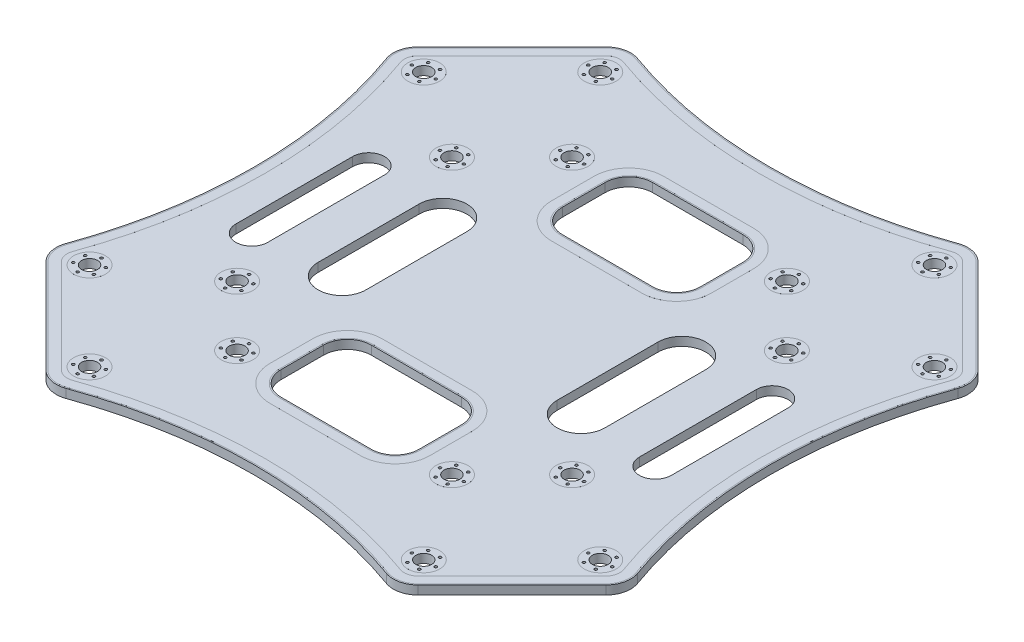
SolidWorks part; units mm, degrees
material "PLA"
ref_plane "Front Plane" through (0, 0, 0) normal (0, 0, 1) x (1, 0, 0)
ref_plane "Top Plane" through (0, 0, 0) normal (0, 1, 0) x (1, 0, 0)
ref_plane "Right Plane" through (0, 0, 0) normal (1, 0, 0) x (0, 0, -1)
sketch "Sketch1" plane through (0, 0, 0) normal (0, 1, 0) x (1, 0, 0)
  line L0 (-48.55, 0) -> (48.55, 0) construction
  line L1 (0, 48.55) -> (0, -48.55) construction
  line L2 (-30.1605, 53.8) -> (30.1605, 53.8) construction
  line L3 (0, 48.55) -> (0, 53.8) construction
  line L4 (-53.8, 30.1605) -> (-53.8, -30.1605) construction
  line L5 (-30.1605, -53.8) -> (30.1605, -53.8) construction
  line L6 (53.8, -30.1605) -> (53.8, 30.1605) construction
  line L7 (35.0464, 52.7056) -> (52.7056, 35.0464)
  line L8 (-52.7056, 35.0464) -> (-35.0464, 52.7056)
  line L9 (-52.7056, -35.0464) -> (-35.0464, -52.7056)
  line L10 (35.0464, -52.7056) -> (52.7056, -35.0464)
  line L11 (-43.876, -43.876) -> (43.876, 43.876) construction
  line L12 (-43.876, 43.876) -> (43.876, -43.876) construction
  line L13 (-31.7403, 54.075) -> (-31.7403, -54.075) construction
  line L14 (-31.7403, -54.075) -> (31.7403, -54.075) construction
  arc A0 (-30.1605, 53.8) -> (30.1605, 53.8) centre (0, 137.8088) ccw
  arc A1 (53.8, 30.1605) -> (53.8, -30.1605) centre (137.8088, 0) ccw
  arc A2 (30.1605, -53.8) -> (-30.1605, -53.8) centre (0, -137.8088) ccw
  arc A3 (-53.8, -30.1605) -> (-53.8, 30.1605) centre (-137.8088, 0) ccw
  arc A4 (-53.8, -30.1605) -> (-52.7056, -35.0464) centre (-49.3995, -31.7403) ccw
  arc A5 (-35.0464, -52.7056) -> (-30.1605, -53.8) centre (-31.7403, -49.3995) ccw
  arc A6 (30.1605, -53.8) -> (35.0464, -52.7056) centre (31.7403, -49.3995) ccw
  arc A7 (52.7056, -35.0464) -> (53.8, -30.1605) centre (49.3995, -31.7403) ccw
  arc A8 (53.8, 30.1605) -> (52.7056, 35.0464) centre (49.3995, 31.7403) ccw
  arc A9 (35.0464, 52.7056) -> (30.1605, 53.8) centre (31.7403, 49.3995) ccw
  arc A10 (-30.1605, 53.8) -> (-35.0464, 52.7056) centre (-31.7403, 49.3995) ccw
  arc A11 (-52.7056, 35.0464) -> (-53.8, 30.1605) centre (-49.3995, 31.7403) ccw
  point P2 (0, 0)
  point P6 (0, 0)
  point P34 (0, 0)
  dimension "D2" = 108.15
  dimension "D4" = 124.1
  dimension "D1" = 97.1
  dimension "D3" = 5.25
  dimension "D5" = 45
extrude "Boss-Extrude1" add sketch "Sketch1" along normal blind 0.825 and the other way blind 0.825
sketch "Sketch2" plane through (0, 0.825, 0) normal (0, 1, 0) x (1, 0, 0)
  line L0 (0, 18) -> (0, -18) construction
  line L1 (0, 35) -> (0, 18) construction
  line L2 (0, -18) -> (0, -35) construction
  line L3 (-13, 26.5) -> (13, 26.5) construction
  line L4 (13, 30.5) -> (13, 22.5)
  line L5 (-13, 30.5) -> (-13, 22.5)
  line L6 (-8.5, 35) -> (8.5, 35)
  line L7 (-8.5, 18) -> (8.5, 18)
  line L8 (-13, -26.5) -> (13, -26.5) construction
  line L9 (-13, -22.5) -> (-13, -30.5)
  line L10 (13, -22.5) -> (13, -30.5)
  line L11 (-8.5, -18) -> (8.5, -18)
  line L12 (-8.5, -35) -> (8.5, -35)
  line L13 (-18, 0) -> (18, 0) construction
  line L14 (-18, 0) -> (-27, 0) construction
  line L15 (18, 0) -> (27, 0) construction
  line L16 (-22.5, 9.5) -> (-22.5, -9.5) construction
  line L17 (22.5, 9.5) -> (22.5, -9.5) construction
  line L18 (-27, -9.5) -> (-27, 9.5)
  line L19 (-18, -9.5) -> (-18, 9.5)
  line L20 (18, -9.5) -> (18, 9.5)
  line L21 (27, -9.5) -> (27, 9.5)
  line L22 (-35, 0) -> (-27, 0) construction
  line L23 (-41, 0) -> (-35, 0) construction
  line L24 (27, 0) -> (35, 0) construction
  line L25 (35, 0) -> (41, 0) construction
  line L26 (-35, 11) -> (-35, -11)
  line L27 (-41, 11) -> (-41, -11)
  line L28 (-38, 11) -> (-38, -11) construction
  line L29 (35, 11) -> (35, -11)
  line L30 (41, 11) -> (41, -11)
  line L31 (38, 11) -> (38, -11) construction
  arc A0 (-8.5, 35) -> (-13, 30.5) centre (-8.5, 30.5) ccw
  arc A1 (13, 30.5) -> (8.5, 35) centre (8.5, 30.5) ccw
  arc A2 (-13, 22.5) -> (-8.5, 18) centre (-8.5, 22.5) ccw
  arc A3 (8.5, 18) -> (13, 22.5) centre (8.5, 22.5) ccw
  arc A4 (-8.5, -18) -> (-13, -22.5) centre (-8.5, -22.5) ccw
  arc A5 (13, -22.5) -> (8.5, -18) centre (8.5, -22.5) ccw
  arc A6 (8.5, -35) -> (13, -30.5) centre (8.5, -30.5) ccw
  arc A7 (-13, -30.5) -> (-8.5, -35) centre (-8.5, -30.5) ccw
  arc A8 (27, 9.5) -> (18, 9.5) centre (22.5, 9.5) ccw
  arc A9 (18, -9.5) -> (27, -9.5) centre (22.5, -9.5) ccw
  arc A10 (-27, -9.5) -> (-18, -9.5) centre (-22.5, -9.5) ccw
  arc A11 (-18, 9.5) -> (-27, 9.5) centre (-22.5, 9.5) ccw
  arc A12 (-35, 11) -> (-41, 11) centre (-38, 11) ccw
  arc A13 (-41, -11) -> (-35, -11) centre (-38, -11) ccw
  arc A14 (41, 11) -> (35, 11) centre (38, 11) ccw
  arc A15 (35, -11) -> (41, -11) centre (38, -11) ccw
  point P5 (0, 26.5)
  point P22 (0, -26.5)
  point P34 (-22.5, 0)
  point P36 (0, 0)
  point P45 (22.5, 0)
  point P64 (-38, 0)
  point P69 (38, 0)
  dimension "D6" = 26
  dimension "D8" = 36
  dimension "D13" = 8
  dimension "D18" = 22
  dimension "D1" = 36
  dimension "D2" = 17
  dimension "D3" = 17
  dimension "D4" = 26
  dimension "D5" = 8
  dimension "D7" = 8
  dimension "D9" = 9
  dimension "D10" = 9
  dimension "D11" = 19
  dimension "D12" = 19
  dimension "D14" = 8
  dimension "D15" = 6
  dimension "D16" = 6
  dimension "D17" = 22
extrude "Cut-Extrude1" cut sketch "Sketch2" against normal up to surface (1.65 mm away) up to face at (0, -0.825, 0)
sketch "Sketch3" plane through (0, 0.825, 0) normal (0, 1, 0) x (1, 0, 0)
  line L0 (-48.0833, -31.4663) -> (-31.4663, -48.0833) construction
  line L1 (-52.7056, -35.0464) -> (-35.0464, -52.7056) construction
  line L2 (-39.7748, -39.7748) -> (-43.876, -43.876) construction
  line L3 (43.876, -43.876) -> (39.7748, -39.7748) construction
  line L4 (31.4663, -48.0833) -> (48.0833, -31.4663) construction
  line L5 (43.876, 43.876) -> (39.7748, 39.7748) construction
  line L6 (31.4663, 48.0833) -> (48.0833, 31.4663) construction
  line L7 (-43.876, 43.876) -> (-39.7748, 39.7748) construction
  line L8 (-31.4663, 48.0833) -> (-48.0833, 31.4663) construction
  line L9 (-35.0464, 52.7056) -> (-52.7056, 35.0464) construction
  line L10 (52.7056, 35.0464) -> (35.0464, 52.7056) construction
  line L11 (35.0464, -52.7056) -> (52.7056, -35.0464) construction
  line L12 (-31.5403, -20.2266) -> (-20.2266, -31.5403) construction
  line L13 (31.5403, -20.2266) -> (20.2266, -31.5403) construction
  line L14 (-31.5403, 20.2266) -> (-20.2266, 31.5403) construction
  line L15 (20.2266, 31.5403) -> (31.5403, 20.2266) construction
  line L16 (-25.8834, -25.8834) -> (-39.7748, -39.7748) construction
  line L17 (-39.7748, 39.7748) -> (-25.8834, 25.8834) construction
  line L18 (39.7748, 39.7748) -> (25.8834, 25.8834) construction
  line L19 (25.8834, -25.8834) -> (39.7748, -39.7748) construction
  line L20 (-20.2266, -31.5403) -> (-31.4663, -48.0833) construction
  line L21 (-31.5403, -20.2266) -> (-48.0833, -31.4663) construction
  circle A0 centre (-48.0833, -31.4663) radius 1.5
  circle A1 centre (-31.4663, -48.0833) radius 1.5
  circle A2 centre (31.4663, -48.0833) radius 1.5
  circle A3 centre (48.0833, -31.4663) radius 1.5
  circle A4 centre (48.0833, 31.4663) radius 1.5
  circle A5 centre (31.4663, 48.0833) radius 1.5
  circle A6 centre (-31.4663, 48.0833) radius 1.5
  circle A7 centre (-48.0833, 31.4663) radius 1.5
  circle A8 centre (-31.5403, -20.2266) radius 1.5
  circle A9 centre (-20.2266, -31.5403) radius 1.5
  circle A10 centre (-31.5403, 20.2266) radius 1.5
  circle A11 centre (-20.2266, 31.5403) radius 1.5
  circle A12 centre (20.2266, 31.5403) radius 1.5
  circle A13 centre (31.5403, 20.2266) radius 1.5
  circle A14 centre (31.5403, -20.2266) radius 1.5
  circle A15 centre (20.2266, -31.5403) radius 1.5
  dimension "D3" = 3
  dimension "D4" = 20
  dimension "D1" = 23.5
  dimension "D2" = 5.8
  dimension "D5" = 16
extrude "Cut-Extrude2" cut sketch "Sketch3" against normal up to surface (1.65 mm away) up to face at (38, -0.825, 0)
sketch "Sketch4" plane through (0, 0.825, 0) normal (0, 1, 0) x (1, 0, 0)
  line L0 (13.25, -30.5) -> (13.25, -22.5)
  line L1 (-13.25, -30.5) -> (-13.25, -22.5)
  line L2 (-8.5, -17.75) -> (8.5, -17.75)
  line L3 (-8.5, -35.25) -> (8.5, -35.25)
  line L4 (13, -30.5) -> (13, -22.5) construction
  line L5 (15.05, -30.5) -> (15.05, -22.5)
  line L6 (-8.5, -15.95) -> (8.5, -15.95)
  line L7 (-15.05, -30.5) -> (-15.05, -22.5)
  line L8 (-8.5, -37.05) -> (8.5, -37.05)
  line L9 (-8.5, 17.75) -> (8.5, 17.75)
  line L10 (-13.25, 22.5) -> (-13.25, 30.5)
  line L11 (-8.5, 35.25) -> (8.5, 35.25)
  line L12 (13.25, 30.5) -> (13.25, 22.5)
  line L13 (13, 22.5) -> (13, 30.5) construction
  line L14 (15.05, 30.5) -> (15.05, 22.5)
  line L15 (-8.5, 15.95) -> (8.5, 15.95)
  line L16 (-15.05, 22.5) -> (-15.05, 30.5)
  line L17 (-8.5, 37.05) -> (8.5, 37.05)
  line L18 (34.8696, -52.5288) -> (52.5288, -34.8696)
  line L19 (35.0464, -52.7056) -> (52.7056, -35.0464) construction
  line L20 (34.8696, 52.5288) -> (52.5288, 34.8696)
  line L21 (52.7056, 35.0464) -> (35.0464, 52.7056) construction
  line L22 (-52.5288, 34.8696) -> (-34.8696, 52.5288)
  line L23 (-35.0464, 52.7056) -> (-52.7056, 35.0464) construction
  line L24 (-52.5288, -34.8696) -> (-34.8696, -52.5288)
  line L25 (-52.7056, -35.0464) -> (-35.0464, -52.7056) construction
  line L26 (-51.256, 33.5968) -> (-33.5968, 51.256)
  line L27 (33.5968, 51.256) -> (51.256, 33.5968)
  line L28 (33.5968, -51.256) -> (51.256, -33.5968)
  line L29 (-51.256, -33.5968) -> (-33.5968, -51.256)
  line L30 (-31.4663, -45.8333) -> (-31.4663, -46.5833) construction
  line L31 (-29.5177, -46.9583) -> (-31.4663, -45.8333) construction
  line L32 (-31.4663, -45.8333) -> (-33.4148, -46.9583) construction
  line L33 (-33.4148, -46.9583) -> (-33.4148, -49.2083) construction
  line L34 (-33.4148, -49.2083) -> (-31.4663, -50.3333) construction
  line L35 (-31.4663, -50.3333) -> (-29.5177, -49.2083) construction
  line L36 (-29.5177, -49.2083) -> (-29.5177, -46.9583) construction
  line L37 (-31.4663, -45.8333) -> (-31.4663, -45.0833) construction
  line L39 (-48.0833, -29.2163) -> (-50.0318, -30.3413) construction
  line L40 (-50.0318, -30.3413) -> (-50.0318, -32.5913) construction
  line L41 (-50.0318, -32.5913) -> (-48.0833, -33.7163) construction
  line L42 (-48.0833, -33.7163) -> (-46.1347, -32.5913) construction
  line L43 (-46.1347, -32.5913) -> (-46.1347, -30.3413) construction
  line L44 (-46.1347, -30.3413) -> (-48.0833, -29.2163) construction
  line L45 (-31.5403, -17.9766) -> (-33.4888, -19.1016) construction
  line L46 (-33.4888, -19.1016) -> (-33.4888, -21.3516) construction
  line L47 (-33.4888, -21.3516) -> (-31.5403, -22.4766) construction
  line L48 (-31.5403, -22.4766) -> (-29.5917, -21.3516) construction
  line L49 (-29.5917, -21.3516) -> (-29.5917, -19.1016) construction
  line L50 (-29.5917, -19.1016) -> (-31.5403, -17.9766) construction
  line L51 (-20.2266, -29.2903) -> (-22.1751, -30.4153) construction
  line L52 (-22.1751, -30.4153) -> (-22.1751, -32.6653) construction
  line L53 (-22.1751, -32.6653) -> (-20.2266, -33.7903) construction
  line L54 (-20.2266, -33.7903) -> (-18.278, -32.6653) construction
  line L55 (-18.278, -32.6653) -> (-18.278, -30.4153) construction
  line L56 (-18.278, -30.4153) -> (-20.2266, -29.2903) construction
  line L57 (20.2266, 33.7903) -> (18.278, 32.6653) construction
  line L58 (18.278, 32.6653) -> (18.278, 30.4153) construction
  line L59 (18.278, 30.4153) -> (20.2266, 29.2903) construction
  line L60 (20.2266, 29.2903) -> (22.1751, 30.4153) construction
  line L61 (22.1751, 30.4153) -> (22.1751, 32.6653) construction
  line L62 (22.1751, 32.6653) -> (20.2266, 33.7903) construction
  line L63 (31.5403, 22.4766) -> (29.5917, 21.3516) construction
  line L64 (29.5917, 21.3516) -> (29.5917, 19.1016) construction
  line L65 (29.5917, 19.1016) -> (31.5403, 17.9766) construction
  line L66 (31.5403, 17.9766) -> (33.4888, 19.1016) construction
  line L67 (33.4888, 19.1016) -> (33.4888, 21.3516) construction
  line L68 (33.4888, 21.3516) -> (31.5403, 22.4766) construction
  line L69 (48.0833, 33.7163) -> (46.1347, 32.5913) construction
  line L70 (46.1347, 32.5913) -> (46.1347, 30.3413) construction
  line L71 (46.1347, 30.3413) -> (48.0833, 29.2163) construction
  line L72 (48.0833, 29.2163) -> (50.0318, 30.3413) construction
  line L73 (50.0318, 30.3413) -> (50.0318, 32.5913) construction
  line L74 (50.0318, 32.5913) -> (48.0833, 33.7163) construction
  line L75 (31.4663, 50.3333) -> (29.5177, 49.2083) construction
  line L76 (29.5177, 49.2083) -> (29.5177, 46.9583) construction
  line L77 (29.5177, 46.9583) -> (31.4663, 45.8333) construction
  line L78 (31.4663, 45.8333) -> (33.4148, 46.9583) construction
  line L79 (33.4148, 46.9583) -> (33.4148, 49.2083) construction
  line L80 (33.4148, 49.2083) -> (31.4663, 50.3333) construction
  line L81 (-50.3333, 31.4663) -> (-49.2083, 29.5177) construction
  line L82 (-49.2083, 29.5177) -> (-46.9583, 29.5177) construction
  line L83 (-46.9583, 29.5177) -> (-45.8333, 31.4663) construction
  line L84 (-45.8333, 31.4663) -> (-46.9583, 33.4148) construction
  line L85 (-46.9583, 33.4148) -> (-49.2083, 33.4148) construction
  line L86 (-49.2083, 33.4148) -> (-50.3333, 31.4663) construction
  line L87 (-33.7903, 20.2266) -> (-32.6653, 18.278) construction
  line L88 (-32.6653, 18.278) -> (-30.4153, 18.278) construction
  line L89 (-30.4153, 18.278) -> (-29.2903, 20.2266) construction
  line L90 (-29.2903, 20.2266) -> (-30.4153, 22.1751) construction
  line L91 (-30.4153, 22.1751) -> (-32.6653, 22.1751) construction
  line L92 (-32.6653, 22.1751) -> (-33.7903, 20.2266) construction
  line L93 (-22.4766, 31.5403) -> (-21.3516, 29.5917) construction
  line L94 (-21.3516, 29.5917) -> (-19.1016, 29.5917) construction
  line L95 (-19.1016, 29.5917) -> (-17.9766, 31.5403) construction
  line L96 (-17.9766, 31.5403) -> (-19.1016, 33.4888) construction
  line L97 (-19.1016, 33.4888) -> (-21.3516, 33.4888) construction
  line L98 (-21.3516, 33.4888) -> (-22.4766, 31.5403) construction
  line L99 (-29.2163, 48.0833) -> (-30.3413, 50.0318) construction
  line L100 (-30.3413, 50.0318) -> (-32.5913, 50.0318) construction
  line L101 (-32.5913, 50.0318) -> (-33.7163, 48.0833) construction
  line L102 (-33.7163, 48.0833) -> (-32.5913, 46.1347) construction
  line L103 (-32.5913, 46.1347) -> (-30.3413, 46.1347) construction
  line L104 (-30.3413, 46.1347) -> (-29.2163, 48.0833) construction
  line L105 (22.4766, -31.5403) -> (21.3516, -29.5917) construction
  line L106 (21.3516, -29.5917) -> (19.1016, -29.5917) construction
  line L107 (19.1016, -29.5917) -> (17.9766, -31.5403) construction
  line L108 (17.9766, -31.5403) -> (19.1016, -33.4888) construction
  line L109 (19.1016, -33.4888) -> (21.3516, -33.4888) construction
  line L110 (21.3516, -33.4888) -> (22.4766, -31.5403) construction
  line L111 (33.7903, -20.2266) -> (32.6653, -18.278) construction
  line L112 (32.6653, -18.278) -> (30.4153, -18.278) construction
  line L113 (30.4153, -18.278) -> (29.2903, -20.2266) construction
  line L114 (29.2903, -20.2266) -> (30.4153, -22.1751) construction
  line L115 (30.4153, -22.1751) -> (32.6653, -22.1751) construction
  line L116 (32.6653, -22.1751) -> (33.7903, -20.2266) construction
  line L117 (33.7163, -48.0833) -> (32.5913, -46.1347) construction
  line L118 (32.5913, -46.1347) -> (30.3413, -46.1347) construction
  line L119 (30.3413, -46.1347) -> (29.2163, -48.0833) construction
  line L120 (29.2163, -48.0833) -> (30.3413, -50.0318) construction
  line L121 (30.3413, -50.0318) -> (32.5913, -50.0318) construction
  line L122 (32.5913, -50.0318) -> (33.7163, -48.0833) construction
  line L123 (50.3333, -31.4663) -> (49.2083, -29.5177) construction
  line L124 (49.2083, -29.5177) -> (46.9583, -29.5177) construction
  line L125 (46.9583, -29.5177) -> (45.8333, -31.4663) construction
  line L126 (45.8333, -31.4663) -> (46.9583, -33.4148) construction
  line L127 (46.9583, -33.4148) -> (49.2083, -33.4148) construction
  line L128 (49.2083, -33.4148) -> (50.3333, -31.4663) construction
  arc A0 (-8.5, -17.75) -> (-13.25, -22.5) centre (-8.5, -22.5) ccw
  arc A1 (13.25, -22.5) -> (8.5, -17.75) centre (8.5, -22.5) ccw
  arc A2 (-13.25, -30.5) -> (-8.5, -35.25) centre (-8.5, -30.5) ccw
  arc A3 (8.5, -35.25) -> (13.25, -30.5) centre (8.5, -30.5) ccw
  arc A4 (8.5, -35) -> (13, -30.5) centre (8.5, -30.5) ccw construction
  arc A5 (13, -22.5) -> (8.5, -18) centre (8.5, -22.5) ccw construction
  arc A6 (-8.5, -18) -> (-13, -22.5) centre (-8.5, -22.5) ccw construction
  arc A7 (-13, -30.5) -> (-8.5, -35) centre (-8.5, -30.5) ccw construction
  arc A8 (15.05, -22.5) -> (8.5, -15.95) centre (8.5, -22.5) ccw
  arc A9 (-8.5, -15.95) -> (-15.05, -22.5) centre (-8.5, -22.5) ccw
  arc A10 (-15.05, -30.5) -> (-8.5, -37.05) centre (-8.5, -30.5) ccw
  arc A11 (8.5, -37.05) -> (15.05, -30.5) centre (8.5, -30.5) ccw
  arc A12 (-13.25, 22.5) -> (-8.5, 17.75) centre (-8.5, 22.5) ccw
  arc A13 (-8.5, 35.25) -> (-13.25, 30.5) centre (-8.5, 30.5) ccw
  arc A14 (13.25, 30.5) -> (8.5, 35.25) centre (8.5, 30.5) ccw
  arc A15 (8.5, 17.75) -> (13.25, 22.5) centre (8.5, 22.5) ccw
  arc A16 (8.5, 18) -> (13, 22.5) centre (8.5, 22.5) ccw construction
  arc A17 (13, 30.5) -> (8.5, 35) centre (8.5, 30.5) ccw construction
  arc A18 (-8.5, 35) -> (-13, 30.5) centre (-8.5, 30.5) ccw construction
  arc A19 (-13, 22.5) -> (-8.5, 18) centre (-8.5, 22.5) ccw construction
  arc A20 (8.5, 15.95) -> (15.05, 22.5) centre (8.5, 22.5) ccw
  arc A21 (-15.05, 22.5) -> (-8.5, 15.95) centre (-8.5, 22.5) ccw
  arc A22 (-8.5, 37.05) -> (-15.05, 30.5) centre (-8.5, 30.5) ccw
  arc A23 (15.05, 30.5) -> (8.5, 37.05) centre (8.5, 30.5) ccw
  arc A24 (30.245, -53.5647) -> (-30.245, -53.5647) centre (0, -137.8088) ccw
  arc A25 (30.1605, -53.8) -> (-30.1605, -53.8) centre (0, -137.8088) ccw construction
  arc A26 (-53.5647, -30.245) -> (-53.5647, 30.245) centre (-137.8088, 0) ccw
  arc A27 (-30.245, 53.5647) -> (30.245, 53.5647) centre (0, 137.8088) ccw
  arc A28 (53.5647, 30.245) -> (53.5647, -30.245) centre (137.8088, 0) ccw
  arc A29 (53.8, 30.1605) -> (53.8, -30.1605) centre (137.8088, 0) ccw construction
  arc A30 (-30.1605, 53.8) -> (30.1605, 53.8) centre (0, 137.8088) ccw construction
  arc A31 (-53.8, -30.1605) -> (-53.8, 30.1605) centre (-137.8088, 0) ccw construction
  arc A32 (34.8696, 52.5288) -> (30.245, 53.5647) centre (31.7403, 49.3995) ccw
  arc A33 (35.0464, 52.7056) -> (30.1605, 53.8) centre (31.7403, 49.3995) ccw construction
  arc A34 (53.5647, 30.245) -> (52.5288, 34.8696) centre (49.3995, 31.7403) ccw
  arc A35 (53.8, 30.1605) -> (52.7056, 35.0464) centre (49.3995, 31.7403) ccw construction
  arc A36 (52.5288, -34.8696) -> (53.5647, -30.245) centre (49.3995, -31.7403) ccw
  arc A37 (52.7056, -35.0464) -> (53.8, -30.1605) centre (49.3995, -31.7403) ccw construction
  arc A38 (30.245, -53.5647) -> (34.8696, -52.5288) centre (31.7403, -49.3995) ccw
  arc A39 (30.1605, -53.8) -> (35.0464, -52.7056) centre (31.7403, -49.3995) ccw construction
  arc A40 (-34.8696, -52.5288) -> (-30.245, -53.5647) centre (-31.7403, -49.3995) ccw
  arc A41 (-35.0464, -52.7056) -> (-30.1605, -53.8) centre (-31.7403, -49.3995) ccw construction
  arc A42 (-53.5647, -30.245) -> (-52.5288, -34.8696) centre (-49.3995, -31.7403) ccw
  arc A43 (-53.8, -30.1605) -> (-52.7056, -35.0464) centre (-49.3995, -31.7403) ccw construction
  arc A44 (-52.5288, 34.8696) -> (-53.5647, 30.245) centre (-49.3995, 31.7403) ccw
  arc A45 (-52.7056, 35.0464) -> (-53.8, 30.1605) centre (-49.3995, 31.7403) ccw construction
  arc A46 (-30.245, 53.5647) -> (-34.8696, 52.5288) centre (-31.7403, 49.3995) ccw
  arc A47 (-30.1605, 53.8) -> (-35.0464, 52.7056) centre (-31.7403, 49.3995) ccw construction
  arc A48 (-51.8706, -30.8532) -> (-51.8706, 30.8532) centre (-137.8088, 0) ccw
  arc A49 (-51.256, 33.5968) -> (-51.8706, 30.8532) centre (-49.3995, 31.7403) ccw
  arc A50 (-30.8532, 51.8706) -> (-33.5968, 51.256) centre (-31.7403, 49.3995) ccw
  arc A51 (-30.8532, 51.8706) -> (30.8532, 51.8706) centre (0, 137.8088) ccw
  arc A52 (33.5968, 51.256) -> (30.8532, 51.8706) centre (31.7403, 49.3995) ccw
  arc A53 (51.8706, 30.8532) -> (51.256, 33.5968) centre (49.3995, 31.7403) ccw
  arc A54 (51.8706, 30.8532) -> (51.8706, -30.8532) centre (137.8088, 0) ccw
  arc A55 (51.256, -33.5968) -> (51.8706, -30.8532) centre (49.3995, -31.7403) ccw
  arc A56 (30.8532, -51.8706) -> (33.5968, -51.256) centre (31.7403, -49.3995) ccw
  arc A57 (30.8532, -51.8706) -> (-30.8532, -51.8706) centre (0, -137.8088) ccw
  arc A58 (-33.5968, -51.256) -> (-30.8532, -51.8706) centre (-31.7403, -49.3995) ccw
  arc A59 (-51.8706, -30.8532) -> (-51.256, -33.5968) centre (-49.3995, -31.7403) ccw
  circle A60 centre (-31.4663, -48.0833) radius 3
  circle A61 centre (-48.0833, -31.4663) radius 3
  circle A62 centre (-31.5403, -20.2266) radius 3
  circle A63 centre (-20.2266, -31.5403) radius 3
  circle A64 centre (-48.0833, 31.4663) radius 3
  circle A65 centre (-31.5403, 20.2266) radius 3
  circle A66 centre (-20.2266, 31.5403) radius 3
  circle A67 centre (-31.4663, 48.0833) radius 3
  circle A68 centre (20.2266, 31.5403) radius 3
  circle A69 centre (31.4663, 48.0833) radius 3
  circle A70 centre (48.0833, 31.4663) radius 3
  circle A71 centre (31.5403, 20.2266) radius 3
  circle A72 centre (20.2266, -31.5403) radius 3
  circle A73 centre (31.5403, -20.2266) radius 3
  circle A74 centre (48.0833, -31.4663) radius 3
  circle A75 centre (31.4663, -48.0833) radius 3
  circle A76 centre (-31.4663, -48.0833) radius 1.5 construction
  circle A77 centre (-48.0833, -31.4663) radius 1.5 construction
  circle A78 centre (-31.5403, -20.2266) radius 1.5 construction
  circle A79 centre (-20.2266, -31.5403) radius 1.5 construction
  circle A80 centre (20.2266, -31.5403) radius 1.5 construction
  circle A81 centre (31.4663, -48.0833) radius 1.5 construction
  circle A82 centre (48.0833, -31.4663) radius 1.5 construction
  circle A83 centre (31.5403, -20.2266) radius 1.5 construction
  circle A84 centre (48.0833, 31.4663) radius 1.5 construction
  circle A85 centre (31.5403, 20.2266) radius 1.5 construction
  circle A86 centre (20.2266, 31.5403) radius 1.5 construction
  circle A87 centre (31.4663, 48.0833) radius 1.5 construction
  circle A88 centre (-20.2266, 31.5403) radius 1.5 construction
  circle A89 centre (-31.5403, 20.2266) radius 1.5 construction
  circle A90 centre (-48.0833, 31.4663) radius 1.5 construction
  circle A91 centre (-31.4663, 48.0833) radius 1.5 construction
  circle A92 centre (-48.0833, -31.4663) radius 1.5
  circle A93 centre (-31.4663, -48.0833) radius 1.5
  circle A94 centre (-20.2266, -31.5403) radius 1.5
  circle A95 centre (-31.5403, -20.2266) radius 1.5
  circle A96 centre (-48.0833, 31.4663) radius 1.5
  circle A97 centre (-31.5403, 20.2266) radius 1.5
  circle A98 centre (-20.2266, 31.5403) radius 1.5
  circle A99 centre (-31.4663, 48.0833) radius 1.5
  circle A100 centre (20.2266, 31.5403) radius 1.5
  circle A101 centre (31.4663, 48.0833) radius 1.5
  circle A102 centre (48.0833, 31.4663) radius 1.5
  circle A103 centre (31.5403, 20.2266) radius 1.5
  circle A104 centre (31.5403, -20.2266) radius 1.5
  circle A105 centre (20.2266, -31.5403) radius 1.5
  circle A106 centre (48.0833, -31.4663) radius 1.5
  circle A107 centre (31.4663, -48.0833) radius 1.5
  circle A108 centre (-31.4663, -48.0833) radius 1.9486 construction
  circle A109 centre (-48.0833, -31.4663) radius 1.9486 construction
  circle A110 centre (-31.5403, -20.2266) radius 1.9486 construction
  circle A111 centre (-20.2266, -31.5403) radius 1.9486 construction
  circle A112 centre (-31.4663, -50.3333) radius 0.25
  circle A113 centre (-29.5177, -49.2083) radius 0.25
  circle A114 centre (-29.5177, -46.9583) radius 0.25
  circle A115 centre (-31.4663, -45.8333) radius 0.25
  circle A116 centre (-33.4148, -46.9583) radius 0.25
  circle A117 centre (-33.4148, -49.2083) radius 0.25
  circle A118 centre (-48.0833, -33.7163) radius 0.25
  circle A119 centre (-46.1347, -32.5913) radius 0.25
  circle A120 centre (-46.1347, -30.3413) radius 0.25
  circle A121 centre (-48.0833, -29.2163) radius 0.25
  circle A122 centre (-50.0318, -30.3413) radius 0.25
  circle A123 centre (-50.0318, -32.5913) radius 0.25
  circle A124 centre (-31.5403, -22.4766) radius 0.25
  circle A125 centre (-29.5917, -21.3516) radius 0.25
  circle A126 centre (-29.5917, -19.1016) radius 0.25
  circle A127 centre (-31.5403, -17.9766) radius 0.25
  circle A128 centre (-33.4888, -19.1016) radius 0.25
  circle A129 centre (-33.4888, -21.3516) radius 0.25
  circle A130 centre (-20.2266, -33.7903) radius 0.25
  circle A131 centre (-18.278, -32.6653) radius 0.25
  circle A132 centre (-18.278, -30.4153) radius 0.25
  circle A133 centre (-20.2266, -29.2903) radius 0.25
  circle A134 centre (-22.1751, -30.4153) radius 0.25
  circle A135 centre (-22.1751, -32.6653) radius 0.25
  circle A136 centre (20.2266, 31.5403) radius 1.9486 construction
  circle A137 centre (31.5403, 20.2266) radius 1.9486 construction
  circle A138 centre (48.0833, 31.4663) radius 1.9486 construction
  circle A139 centre (31.4663, 48.0833) radius 1.9486 construction
  circle A140 centre (20.2266, 29.2903) radius 0.25
  circle A141 centre (22.1751, 30.4153) radius 0.25
  circle A142 centre (22.1751, 32.6653) radius 0.25
  circle A143 centre (18.278, 30.4153) radius 0.25
  circle A144 centre (18.278, 32.6653) radius 0.25
  circle A145 centre (20.2266, 33.7903) radius 0.25
  circle A146 centre (31.4663, 45.8333) radius 0.25
  circle A147 centre (29.5177, 46.9583) radius 0.25
  circle A148 centre (29.5177, 49.2083) radius 0.25
  circle A149 centre (31.4663, 50.3333) radius 0.25
  circle A150 centre (33.4148, 49.2083) radius 0.25
  circle A151 centre (33.4148, 46.9583) radius 0.25
  circle A152 centre (29.5917, 21.3516) radius 0.25
  circle A153 centre (29.5917, 19.1016) radius 0.25
  circle A154 centre (31.5403, 17.9766) radius 0.25
  circle A155 centre (33.4888, 19.1016) radius 0.25
  circle A156 centre (33.4888, 21.3516) radius 0.25
  circle A157 centre (31.5403, 22.4766) radius 0.25
  circle A158 centre (48.0833, 29.2163) radius 0.25
  circle A159 centre (46.1347, 30.3413) radius 0.25
  circle A160 centre (50.0318, 30.3413) radius 0.25
  circle A161 centre (50.0318, 32.5913) radius 0.25
  circle A162 centre (48.0833, 33.7163) radius 0.25
  circle A163 centre (46.1347, 32.5913) radius 0.25
  circle A164 centre (-48.0833, 31.4663) radius 1.9486 construction
  circle A165 centre (-31.5403, 20.2266) radius 1.9486 construction
  circle A166 centre (-20.2266, 31.5403) radius 1.9486 construction
  circle A167 centre (-31.4663, 48.0833) radius 1.9486 construction
  circle A168 centre (-46.9583, 29.5177) radius 0.25
  circle A169 centre (-45.8333, 31.4663) radius 0.25
  circle A170 centre (-46.9583, 33.4148) radius 0.25
  circle A171 centre (-49.2083, 33.4148) radius 0.25
  circle A172 centre (-50.3333, 31.4663) radius 0.25
  circle A173 centre (-49.2083, 29.5177) radius 0.25
  circle A174 centre (-32.6653, 18.278) radius 0.25
  circle A175 centre (-33.7903, 20.2266) radius 0.25
  circle A176 centre (-32.6653, 22.1751) radius 0.25
  circle A177 centre (-30.4153, 22.1751) radius 0.25
  circle A178 centre (-29.2903, 20.2266) radius 0.25
  circle A179 centre (-30.4153, 18.278) radius 0.25
  circle A180 centre (-19.1016, 29.5917) radius 0.25
  circle A181 centre (-21.3516, 29.5917) radius 0.25
  circle A182 centre (-22.4766, 31.5403) radius 0.25
  circle A183 centre (-21.3516, 33.4888) radius 0.25
  circle A184 centre (-19.1016, 33.4888) radius 0.25
  circle A185 centre (-17.9766, 31.5403) radius 0.25
  circle A186 centre (-32.5913, 46.1347) radius 0.25
  circle A187 centre (-33.7163, 48.0833) radius 0.25
  circle A188 centre (-32.5913, 50.0318) radius 0.25
  circle A189 centre (-30.3413, 50.0318) radius 0.25
  circle A190 centre (-29.2163, 48.0833) radius 0.25
  circle A191 centre (-30.3413, 46.1347) radius 0.25
  circle A192 centre (20.2266, -31.5403) radius 1.9486 construction
  circle A193 centre (31.5403, -20.2266) radius 1.9486 construction
  circle A194 centre (31.4663, -48.0833) radius 1.9486 construction
  circle A195 centre (48.0833, -31.4663) radius 1.9486 construction
  circle A196 centre (19.1016, -33.4888) radius 0.25
  circle A197 centre (21.3516, -33.4888) radius 0.25
  circle A198 centre (22.4766, -31.5403) radius 0.25
  circle A199 centre (21.3516, -29.5917) radius 0.25
  circle A200 centre (19.1016, -29.5917) radius 0.25
  circle A201 centre (17.9766, -31.5403) radius 0.25
  circle A202 centre (30.3413, -50.0318) radius 0.25
  circle A203 centre (29.2163, -48.0833) radius 0.25
  circle A204 centre (30.3413, -46.1347) radius 0.25
  circle A205 centre (32.5913, -46.1347) radius 0.25
  circle A206 centre (33.7163, -48.0833) radius 0.25
  circle A207 centre (32.5913, -50.0318) radius 0.25
  circle A208 centre (46.9583, -33.4148) radius 0.25
  circle A209 centre (45.8333, -31.4663) radius 0.25
  circle A210 centre (46.9583, -29.5177) radius 0.25
  circle A211 centre (49.2083, -29.5177) radius 0.25
  circle A212 centre (50.3333, -31.4663) radius 0.25
  circle A213 centre (49.2083, -33.4148) radius 0.25
  circle A214 centre (30.4153, -22.1751) radius 0.25
  circle A215 centre (29.2903, -20.2266) radius 0.25
  circle A216 centre (30.4153, -18.278) radius 0.25
  circle A217 centre (32.6653, -18.278) radius 0.25
  circle A218 centre (33.7903, -20.2266) radius 0.25
  circle A219 centre (32.6653, -22.1751) radius 0.25
  dimension "D1" = 0.25
  dimension "D3" = 0.25
  dimension "D5" = 0.25
  dimension "D7" = 6
  dimension "D8" = 0.5
  dimension "D2" = 1.8
  dimension "D4" = 1.8
  dimension "D6" = 1.8
extrude "Boss-Extrude2" add sketch "Sketch4" along normal blind 0.001 contours A27 A46 L22 A44 A26 A42 L24 A40 A24 A38 L18 A36 A28 A34 L20 A32 A59 A48 A49 L26 A50 A51 A52 L27 A53 A54 A55 L28 A56 A57 A58 L29 | L8 A11 L5 A8 L6 A9 L7 A10 A3 L3 A2 L1 A0 L2 A1 L0 | L14 A23 L17 A22 L16 A21 L15 A20 A15 L9 A12 L10 A13 L11 A14 L12 | A61 A92 | A60 A93 | A63 A94 | A62 A95 | A75 A107 | A72 A105 | A73 A104 | A74 A106 | A71 A103 | A70 A102 | A68 A100 | A69 A101 | A64 A96 | A65 A97 | A66 A98 | A67 A99 region at (12.8716, 0.825, 34.8716) region at (14.6824, 0.825, -26.5) region at (32.3749, 0.825, 52.2324) region at (-34.3814, 0.825, 48.0833) region at (-50.9984, 0.825, 31.4663) region at (-34.4554, 0.825, 20.2266) region at (-23.1417, 0.825, 31.5403) region at (-50.9984, 0.825, -31.4663) region at (-34.4554, 0.825, -20.2266) region at (-23.1417, 0.825, -31.5403) region at (-34.3814, 0.825, -48.0833) region at (17.3114, 0.825, -31.5403) region at (28.5511, 0.825, -48.0833) region at (45.1681, 0.825, -31.4663) region at (28.6251, 0.825, -20.2266) region at (17.3114, 0.825, 31.5403) region at (28.6251, 0.825, 20.2266) region at (45.1681, 0.825, 31.4663) region at (28.5511, 0.825, 48.0833)
mirror "Mirror2" about plane through (0, 0, 0) normal (0, 1, 0) of "Boss-Extrude2"
sketch "Sketch5" plane through (0, 0.825, 0) normal (0, 1, 0) x (1, 0, 0)
  circle A0 centre (-31.4663, -45.8333) radius 0.25
  circle A1 centre (-29.5177, -46.9583) radius 0.25
  circle A2 centre (-29.5177, -49.2083) radius 0.25
  circle A3 centre (-31.4663, -50.3333) radius 0.25
  circle A4 centre (-33.4148, -49.2083) radius 0.25
  circle A5 centre (-33.4148, -46.9583) radius 0.25
  circle A6 centre (-48.0833, -33.7163) radius 0.25
  circle A7 centre (-50.0318, -32.5913) radius 0.25
  circle A8 centre (-50.0318, -30.3413) radius 0.25
  circle A9 centre (-48.0833, -29.2163) radius 0.25
  circle A10 centre (-46.1347, -30.3413) radius 0.25
  circle A11 centre (-46.1347, -32.5913) radius 0.25
  circle A12 centre (-33.4888, -21.3516) radius 0.25
  circle A13 centre (-33.4888, -19.1016) radius 0.25
  circle A14 centre (-31.5403, -17.9766) radius 0.25
  circle A15 centre (-29.5917, -19.1016) radius 0.25
  circle A16 centre (-29.5917, -21.3516) radius 0.25
  circle A17 centre (-31.5403, -22.4766) radius 0.25
  circle A18 centre (-22.1751, -30.4153) radius 0.25
  circle A19 centre (-22.1751, -32.6653) radius 0.25
  circle A20 centre (-20.2266, -33.7903) radius 0.25
  circle A21 centre (-18.278, -32.6653) radius 0.25
  circle A22 centre (-18.278, -30.4153) radius 0.25
  circle A23 centre (-20.2266, -29.2903) radius 0.25
  circle A24 centre (-31.4663, -50.3333) radius 0.25 construction
  circle A25 centre (-33.4148, -49.2083) radius 0.25 construction
  circle A26 centre (-33.4148, -46.9583) radius 0.25 construction
  circle A27 centre (-31.4663, -45.8333) radius 0.25 construction
  circle A28 centre (-29.5177, -46.9583) radius 0.25 construction
  circle A29 centre (-29.5177, -49.2083) radius 0.25 construction
  circle A30 centre (-48.0833, -33.7163) radius 0.25 construction
  circle A31 centre (-50.0318, -32.5913) radius 0.25 construction
  circle A32 centre (-50.0318, -30.3413) radius 0.25 construction
  circle A33 centre (-48.0833, -29.2163) radius 0.25 construction
  circle A34 centre (-46.1347, -30.3413) radius 0.25 construction
  circle A35 centre (-46.1347, -32.5913) radius 0.25 construction
  circle A36 centre (-31.5403, -22.4766) radius 0.25 construction
  circle A37 centre (-33.4888, -21.3516) radius 0.25 construction
  circle A38 centre (-33.4888, -19.1016) radius 0.25 construction
  circle A39 centre (-31.5403, -17.9766) radius 0.25 construction
  circle A40 centre (-29.5917, -19.1016) radius 0.25 construction
  circle A41 centre (-29.5917, -21.3516) radius 0.25 construction
  circle A42 centre (-22.1751, -32.6653) radius 0.25 construction
  circle A43 centre (-22.1751, -30.4153) radius 0.25 construction
  circle A44 centre (-20.2266, -29.2903) radius 0.25 construction
  circle A45 centre (-18.278, -30.4153) radius 0.25 construction
  circle A46 centre (-18.278, -32.6653) radius 0.25 construction
  circle A47 centre (-20.2266, -33.7903) radius 0.25 construction
  circle A48 centre (19.1016, -33.4888) radius 0.25
  circle A49 centre (17.9766, -31.5403) radius 0.25
  circle A50 centre (19.1016, -29.5917) radius 0.25
  circle A51 centre (21.3516, -29.5917) radius 0.25
  circle A52 centre (22.4766, -31.5403) radius 0.25
  circle A53 centre (21.3516, -33.4888) radius 0.25
  circle A54 centre (19.1016, -33.4888) radius 0.25 construction
  circle A55 centre (21.3516, -33.4888) radius 0.25 construction
  circle A56 centre (17.9766, -31.5403) radius 0.25 construction
  circle A57 centre (19.1016, -29.5917) radius 0.25 construction
  circle A58 centre (21.3516, -29.5917) radius 0.25 construction
  circle A59 centre (22.4766, -31.5403) radius 0.25 construction
  circle A60 centre (29.2903, -20.2266) radius 0.25
  circle A61 centre (30.4153, -18.278) radius 0.25
  circle A62 centre (32.6653, -18.278) radius 0.25
  circle A63 centre (30.4153, -22.1751) radius 0.25
  circle A64 centre (32.6653, -22.1751) radius 0.25
  circle A65 centre (33.7903, -20.2266) radius 0.25
  circle A66 centre (29.2903, -20.2266) radius 0.25 construction
  circle A67 centre (30.4153, -18.278) radius 0.25 construction
  circle A68 centre (32.6653, -18.278) radius 0.25 construction
  circle A69 centre (30.4153, -22.1751) radius 0.25 construction
  circle A70 centre (32.6653, -22.1751) radius 0.25 construction
  circle A71 centre (33.7903, -20.2266) radius 0.25 construction
  circle A72 centre (46.9583, -29.5177) radius 0.25
  circle A73 centre (49.2083, -29.5177) radius 0.25
  circle A74 centre (45.8333, -31.4663) radius 0.25
  circle A75 centre (46.9583, -33.4148) radius 0.25
  circle A76 centre (49.2083, -33.4148) radius 0.25
  circle A77 centre (50.3333, -31.4663) radius 0.25
  circle A78 centre (45.8333, -31.4663) radius 0.25 construction
  circle A79 centre (46.9583, -29.5177) radius 0.25 construction
  circle A80 centre (49.2083, -29.5177) radius 0.25 construction
  circle A81 centre (50.3333, -31.4663) radius 0.25 construction
  circle A82 centre (49.2083, -33.4148) radius 0.25 construction
  circle A83 centre (46.9583, -33.4148) radius 0.25 construction
  circle A84 centre (30.3413, -46.1347) radius 0.25
  circle A85 centre (32.5913, -46.1347) radius 0.25
  circle A86 centre (29.2163, -48.0833) radius 0.25
  circle A87 centre (30.3413, -50.0318) radius 0.25
  circle A88 centre (32.5913, -50.0318) radius 0.25
  circle A89 centre (33.7163, -48.0833) radius 0.25
  circle A90 centre (29.2163, -48.0833) radius 0.25 construction
  circle A91 centre (30.3413, -46.1347) radius 0.25 construction
  circle A92 centre (32.5913, -46.1347) radius 0.25 construction
  circle A93 centre (30.3413, -50.0318) radius 0.25 construction
  circle A94 centre (32.5913, -50.0318) radius 0.25 construction
  circle A95 centre (33.7163, -48.0833) radius 0.25 construction
  circle A96 centre (-32.6653, 18.278) radius 0.25
  circle A97 centre (-33.7903, 20.2266) radius 0.25
  circle A98 centre (-32.6653, 22.1751) radius 0.25
  circle A99 centre (-30.4153, 22.1751) radius 0.25
  circle A100 centre (-29.2903, 20.2266) radius 0.25
  circle A101 centre (-30.4153, 18.278) radius 0.25
  circle A102 centre (-32.6653, 18.278) radius 0.25 construction
  circle A103 centre (-33.7903, 20.2266) radius 0.25 construction
  circle A104 centre (-32.6653, 22.1751) radius 0.25 construction
  circle A105 centre (-30.4153, 22.1751) radius 0.25 construction
  circle A106 centre (-29.2903, 20.2266) radius 0.25 construction
  circle A107 centre (-30.4153, 18.278) radius 0.25 construction
  circle A108 centre (-49.2083, 29.5177) radius 0.25
  circle A109 centre (-50.3333, 31.4663) radius 0.25
  circle A110 centre (-49.2083, 33.4148) radius 0.25
  circle A111 centre (-46.9583, 33.4148) radius 0.25
  circle A112 centre (-45.8333, 31.4663) radius 0.25
  circle A113 centre (-46.9583, 29.5177) radius 0.25
  circle A114 centre (-49.2083, 29.5177) radius 0.25 construction
  circle A115 centre (-50.3333, 31.4663) radius 0.25 construction
  circle A116 centre (-49.2083, 33.4148) radius 0.25 construction
  circle A117 centre (-46.9583, 33.4148) radius 0.25 construction
  circle A118 centre (-45.8333, 31.4663) radius 0.25 construction
  circle A119 centre (-46.9583, 29.5177) radius 0.25 construction
  circle A120 centre (-32.5913, 46.1347) radius 0.25
  circle A121 centre (-33.7163, 48.0833) radius 0.25
  circle A122 centre (-32.5913, 50.0318) radius 0.25
  circle A123 centre (-30.3413, 50.0318) radius 0.25
  circle A124 centre (-29.2163, 48.0833) radius 0.25
  circle A125 centre (-30.3413, 46.1347) radius 0.25
  circle A126 centre (-32.5913, 46.1347) radius 0.25 construction
  circle A127 centre (-33.7163, 48.0833) radius 0.25 construction
  circle A128 centre (-32.5913, 50.0318) radius 0.25 construction
  circle A129 centre (-30.3413, 50.0318) radius 0.25 construction
  circle A130 centre (-29.2163, 48.0833) radius 0.25 construction
  circle A131 centre (-30.3413, 46.1347) radius 0.25 construction
  circle A132 centre (-21.3516, 29.5917) radius 0.25
  circle A133 centre (-22.4766, 31.5403) radius 0.25
  circle A134 centre (-21.3516, 33.4888) radius 0.25
  circle A135 centre (-19.1016, 33.4888) radius 0.25
  circle A136 centre (-17.9766, 31.5403) radius 0.25
  circle A137 centre (-19.1016, 29.5917) radius 0.25
  circle A138 centre (-21.3516, 29.5917) radius 0.25 construction
  circle A139 centre (-22.4766, 31.5403) radius 0.25 construction
  circle A140 centre (-21.3516, 33.4888) radius 0.25 construction
  circle A141 centre (-19.1016, 33.4888) radius 0.25 construction
  circle A142 centre (-17.9766, 31.5403) radius 0.25 construction
  circle A143 centre (-19.1016, 29.5917) radius 0.25 construction
  circle A144 centre (20.2266, 29.2903) radius 0.25
  circle A145 centre (18.278, 30.4153) radius 0.25
  circle A146 centre (18.278, 32.6653) radius 0.25
  circle A147 centre (20.2266, 33.7903) radius 0.25
  circle A148 centre (22.1751, 32.6653) radius 0.25
  circle A149 centre (22.1751, 30.4153) radius 0.25
  circle A150 centre (20.2266, 29.2903) radius 0.25 construction
  circle A151 centre (18.278, 30.4153) radius 0.25 construction
  circle A152 centre (18.278, 32.6653) radius 0.25 construction
  circle A153 centre (20.2266, 33.7903) radius 0.25 construction
  circle A154 centre (22.1751, 32.6653) radius 0.25 construction
  circle A155 centre (22.1751, 30.4153) radius 0.25 construction
  circle A156 centre (29.5917, 21.3516) radius 0.25
  circle A157 centre (31.5403, 22.4766) radius 0.25
  circle A158 centre (29.5917, 19.1016) radius 0.25
  circle A159 centre (31.5403, 17.9766) radius 0.25
  circle A160 centre (33.4888, 19.1016) radius 0.25
  circle A161 centre (33.4888, 21.3516) radius 0.25
  circle A162 centre (29.5917, 21.3516) radius 0.25 construction
  circle A163 centre (29.5917, 19.1016) radius 0.25 construction
  circle A164 centre (31.5403, 22.4766) radius 0.25 construction
  circle A165 centre (31.5403, 17.9766) radius 0.25 construction
  circle A166 centre (33.4888, 19.1016) radius 0.25 construction
  circle A167 centre (33.4888, 21.3516) radius 0.25 construction
  circle A168 centre (48.0833, 29.2163) radius 0.25
  circle A169 centre (50.0318, 30.3413) radius 0.25
  circle A170 centre (50.0318, 32.5913) radius 0.25
  circle A171 centre (48.0833, 33.7163) radius 0.25
  circle A172 centre (46.1347, 32.5913) radius 0.25
  circle A173 centre (46.1347, 30.3413) radius 0.25
  circle A174 centre (46.1347, 30.3413) radius 0.25 construction
  circle A175 centre (48.0833, 29.2163) radius 0.25 construction
  circle A176 centre (50.0318, 30.3413) radius 0.25 construction
  circle A177 centre (50.0318, 32.5913) radius 0.25 construction
  circle A178 centre (48.0833, 33.7163) radius 0.25 construction
  circle A179 centre (46.1347, 32.5913) radius 0.25 construction
  circle A180 centre (31.4663, 45.8333) radius 0.25
  circle A181 centre (29.5177, 46.9583) radius 0.25
  circle A182 centre (29.5177, 49.2083) radius 0.25
  circle A183 centre (31.4663, 50.3333) radius 0.25
  circle A184 centre (33.4148, 49.2083) radius 0.25
  circle A185 centre (33.4148, 46.9583) radius 0.25
  circle A186 centre (31.4663, 45.8333) radius 0.25 construction
  circle A187 centre (29.5177, 46.9583) radius 0.25 construction
  circle A188 centre (29.5177, 49.2083) radius 0.25 construction
  circle A189 centre (31.4663, 50.3333) radius 0.25 construction
  circle A190 centre (33.4148, 49.2083) radius 0.25 construction
  circle A191 centre (33.4148, 46.9583) radius 0.25 construction
extrude "Cut-Extrude3" cut sketch "Sketch5" against normal up to surface (1.65 mm away) up to face at (-31.4663, -0.825, -45.0833)
